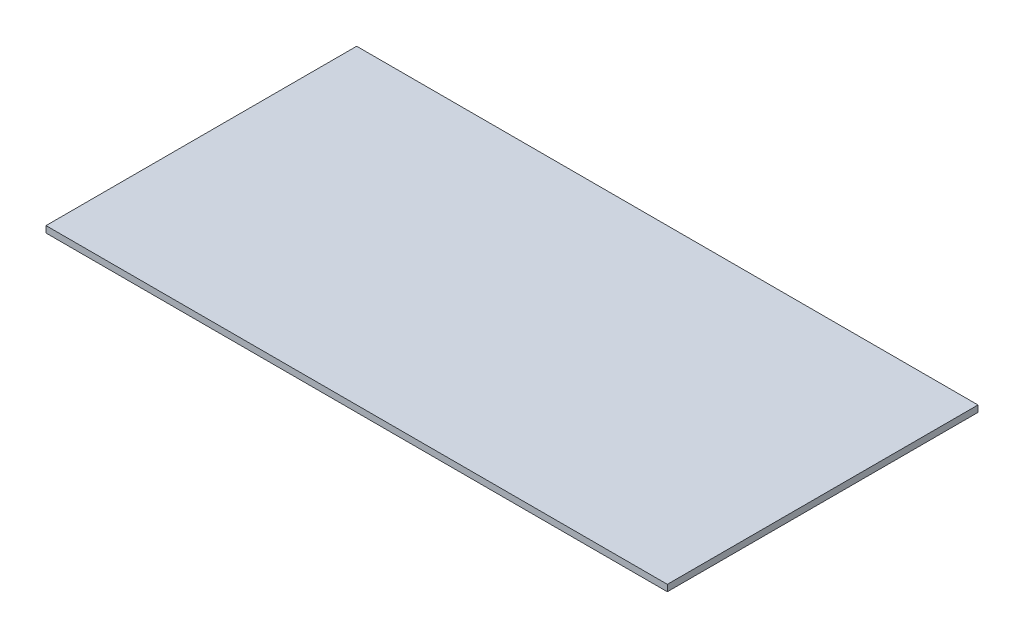
SolidWorks part; units mm, degrees
material "Acrylic (Medium-high impact)"
ref_plane "Front Plane" through (0, 0, 0) normal (0, 0, 1) x (1, 0, 0)
ref_plane "Top Plane" through (0, 0, 0) normal (0, 1, 0) x (1, 0, 0)
ref_plane "Right Plane" through (0, 0, 0) normal (1, 0, 0) x (0, 0, -1)
sketch "Sketch1" plane through (0, 0, 0) normal (0, 1, 0) x (1, 0, 0)
  line L1 (0, 0) -> (1219.2, 0)
  line L2 (0, 0) -> (0, 609.6)
  line L3 (0, 609.6) -> (1219.2, 609.6)
  line L4 (1219.2, 0) -> (1219.2, 609.6)
  dimension "D1" = 609.6
  dimension "D2" = 1219.2
extrude "Boss-Extrude1" add sketch "Sketch1" along normal blind 12.7
